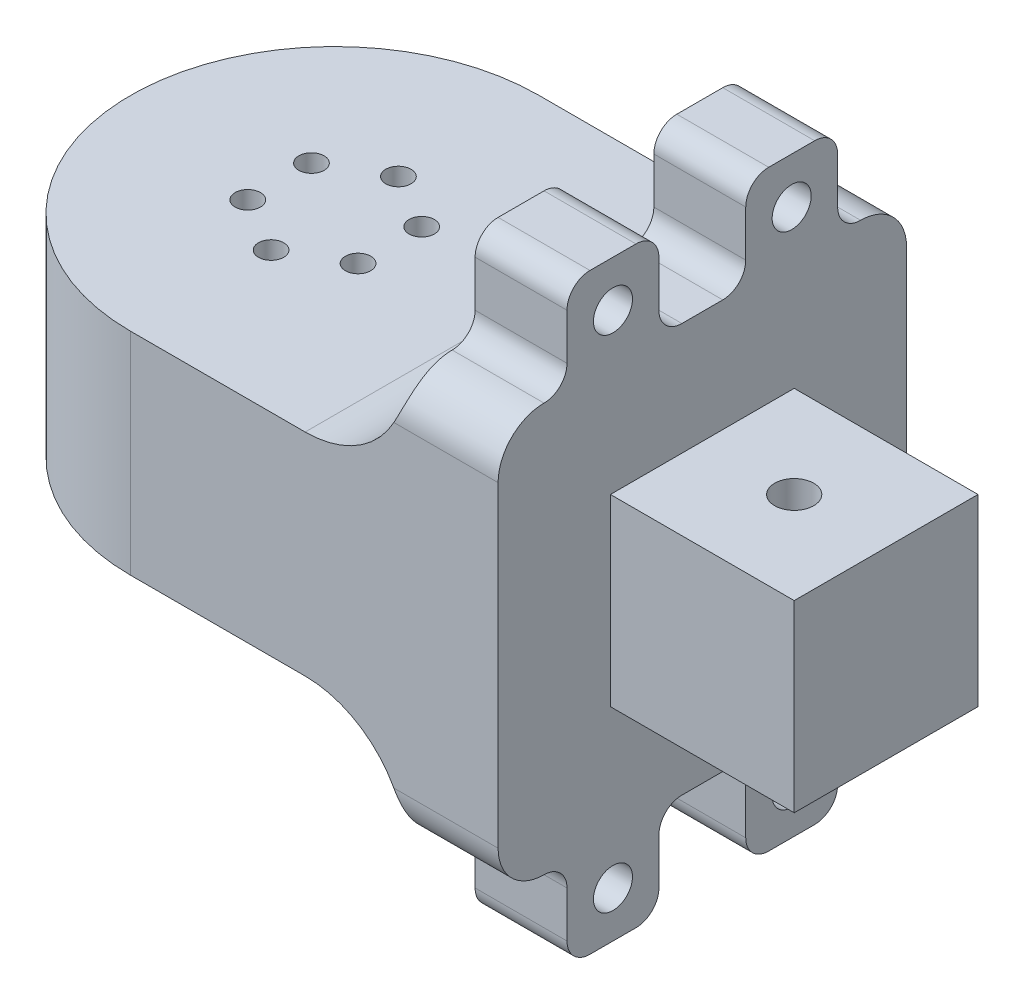
SolidWorks part; units mm, degrees
ref_plane "Front Plane" through (0, 0, 0) normal (0, 0, 1) x (1, 0, 0)
ref_plane "Top Plane" through (0, 0, 0) normal (0, 1, 0) x (1, 0, 0)
ref_plane "Right Plane" through (0, 0, 0) normal (1, 0, 0) x (0, 0, -1)
sketch "Sketch1" plane through (0, 0, 0) normal (0, 1, 0) x (1, 0, 0)
  line L0 (0, 44.45) -> (60, 44.45)
  line L1 (60, 44.45) -> (60, -44.45)
  line L2 (60, -44.45) -> (0, -44.45)
  arc A0 (0, 44.45) -> (0, -44.45) centre (0, 0) ccw
  dimension "D1" = 44.45
  dimension "D2" = 60
extrude "Boss-Extrude1" add sketch "Sketch1" along normal blind 46
sketch "Sketch2" plane through (0, 0, 0) normal (0, -1, 0) x (-1, 0, 0)
  line L1 (0, -13.8564) -> (12, -6.9282)
  line L2 (12, -6.9282) -> (12, 6.9282)
  line L3 (12, 6.9282) -> (0, 13.8564)
  line L4 (0, 13.8564) -> (-12, 6.9282)
  line L5 (-12, 6.9282) -> (-12, -6.9282)
  line L6 (-12, -6.9282) -> (0, -13.8564)
  circle A0 centre (0, 0) radius 12 construction
  circle A1 centre (0, -13.8564) radius 2.75
  circle A2 centre (12, -6.9282) radius 2.75
  circle A3 centre (12, 6.9282) radius 2.75
  circle A4 centre (0, 13.8564) radius 2.75
  circle A5 centre (-12, 6.9282) radius 2.75
  circle A6 centre (-12, -6.9282) radius 2.75
extrude "Cut-Extrude2" cut sketch "Sketch2" against normal blind 76 contours L6 A1 L1 | L5 A6 L6 | L4 A5 L5 | L3 A4 L4 | L2 A3 L3 | L1 A2 L2 | L2 A2 L1 | L1 A1 L6 | L6 A6 L5 | L5 A5 L4 | L4 A4 L3 | L3 A3 L2 region at (0, 0, 12.3403) region at (0, 0, 14.6145) region at (-10.687, 0, 6.1701) region at (-12.6565, 0, 7.3072) region at (12.6565, 0, 7.3072) region at (10.687, 0, 6.1701) region at (-10.687, 0, -6.1701) region at (-12.6565, 0, -7.3072) region at (12.6565, 0, -7.3072) region at (10.687, 0, -6.1701) region at (0, 0, -12.3403) region at (0, 0, -14.6145)
sketch "Sketch3" plane through (60, 0, 0) normal (1, 0, 0) x (0, 0, -1)
  line L2 (-44.45, 67.45) -> (-44.45, -21.45)
  line L4 (-44.45, 67.45) -> (44.45, 67.45)
  line L5 (44.45, 67.45) -> (44.45, -21.45)
  line L6 (-44.45, -21.45) -> (44.45, -21.45)
  dimension "D1" = 88.9
  dimension "D2" = 88.9
extrude "Boss-Extrude2" add sketch "Sketch3" along normal blind 20
fillet "Fillet1" radius 22 2 edges at (60, 46, 0) (60, 0, 0)
sketch "Sketch5" plane through (80, 0, 0) normal (1, 0, 0) x (0, 0, -1)
  line L0 (0, 23) -> (0, 43)
  line L1 (0, 43) -> (-20, 43)
  line L2 (-20, 43) -> (-20, 3)
  line L3 (-20, 3) -> (20, 3)
  line L4 (20, 3) -> (20, 43)
  line L5 (20, 43) -> (0, 43)
  dimension "D1" = 20
extrude "Boss-Extrude3" add sketch "Sketch5" along normal blind 40 contours L4 L5 L1 L2 L3 region at (80, 42.4343, -10)
sketch "Sketch6" plane through (0, 43, 0) normal (0, 1, 0) x (1, 0, 0)
  line L0 (120, 20) -> (120, -20) construction
  circle A0 centre (100, 0) radius 4.25
  dimension "D1" = 20
extrude "Cut-Extrude3" cut sketch "Sketch6" against normal blind 67
sketch "Sketch7" plane through (0, 67.45, 0) normal (0, 1, 0) x (1, 0, 0)
  line L0 (60, 44.45) -> (60, -44.45) construction
  line L1 (60, 29.45) -> (80, 29.45)
  line L2 (60, 29.45) -> (60, 9.45)
  line L3 (60, 9.45) -> (80, 9.45)
  line L4 (80, 29.45) -> (80, 9.45)
  line L5 (80, 20) -> (80, -20) construction
  line L6 (80, 44.45) -> (60, 44.45) construction
  line L7 (80, 44.45) -> (80, -44.45) construction
  line L8 (60, -9.45) -> (80, -9.45)
  line L9 (60, -9.45) -> (60, -29.45)
  line L10 (60, -29.45) -> (80, -29.45)
  line L11 (80, -9.45) -> (80, -29.45)
  line L12 (80, -44.45) -> (60, -44.45) construction
  dimension "D1" = 20
  dimension "D2" = 15
  dimension "D3" = 20
  dimension "D4" = 15
extrude "Boss-Extrude4" add sketch "Sketch7" along normal blind 20
sketch "Sketch8" plane through (0, -21.45, 0) normal (0, -1, 0) x (1, 0, 0)
  line L0 (60, 44.45) -> (60, -44.45) construction
  line L1 (60, 29.45) -> (80, 29.45)
  line L2 (60, 29.45) -> (60, 9.45)
  line L3 (60, 9.45) -> (80, 9.45)
  line L4 (80, 29.45) -> (80, 9.45)
  line L5 (80, 44.45) -> (80, -44.45) construction
  line L6 (80, 44.45) -> (60, 44.45) construction
  line L7 (80, 20) -> (80, -20) construction
  line L8 (60, -29.45) -> (80, -29.45)
  line L9 (60, -29.45) -> (60, -9.45)
  line L10 (60, -9.45) -> (80, -9.45)
  line L11 (80, -29.45) -> (80, -9.45)
  line L12 (80, -44.45) -> (60, -44.45) construction
  dimension "D1" = 20
  dimension "D2" = 15
  dimension "D3" = 20
  dimension "D4" = 15
extrude "Boss-Extrude5" add sketch "Sketch8" along normal blind 20
fillet "Fillet2" radius 5 16 edges at (70, -41.45, -29.45) (70, -41.45, 29.45) (70, 87.45, -9.45) (70, 87.45, -29.45) (70, 87.45, 9.45) (70, 87.45, 29.45) (70, -41.45, -9.45) (70, -41.45, 9.45) (70, -21.45, -29.45) (70, -21.45, -9.45) (70, -21.45, 9.45) (70, -21.45, 29.45) (70, 67.45, 29.45) (70, 67.45, -29.45) (70, 67.45, -9.45) (70, 67.45, 9.45)
fillet "Fillet3" radius 10 4 edges at (70, -21.45, -44.45) (70, 67.45, -44.45) (70, 67.45, 44.45) (70, -21.45, 44.45)
sketch "Sketch10" plane through (60, 0, 0) normal (-1, 0, 0) x (0, 0, 1)
  line L0 (-24.45, 87.45) -> (-14.45, 87.45) construction
  line L1 (-9.45, 82.45) -> (-9.45, 72.45) construction
  line L2 (9.45, 82.45) -> (9.45, 72.45) construction
  line L3 (14.45, 87.45) -> (24.45, 87.45) construction
  line L4 (29.45, -36.45) -> (29.45, -26.45) construction
  line L5 (24.45, -41.45) -> (14.45, -41.45) construction
  line L6 (-14.45, -41.45) -> (-24.45, -41.45) construction
  line L7 (-29.45, -36.45) -> (-29.45, -26.45) construction
  circle A0 centre (-19.45, 77.45) radius 4.25
  circle A1 centre (19.45, 77.45) radius 4.25
  circle A2 centre (19.45, -31.45) radius 4.25
  circle A3 centre (-19.45, -31.45) radius 4.25
  point P22 (0, 0)
  point P24 (-16.5274, -32.4359)
  dimension "D1" = 10
  dimension "D2" = 10
  dimension "D3" = 10
  dimension "D4" = 10
  dimension "D5" = 10
  dimension "D6" = 10
  dimension "D7" = 10
  dimension "D8" = 10
extrude "Cut-Extrude4" cut sketch "Sketch10" against normal blind 20
